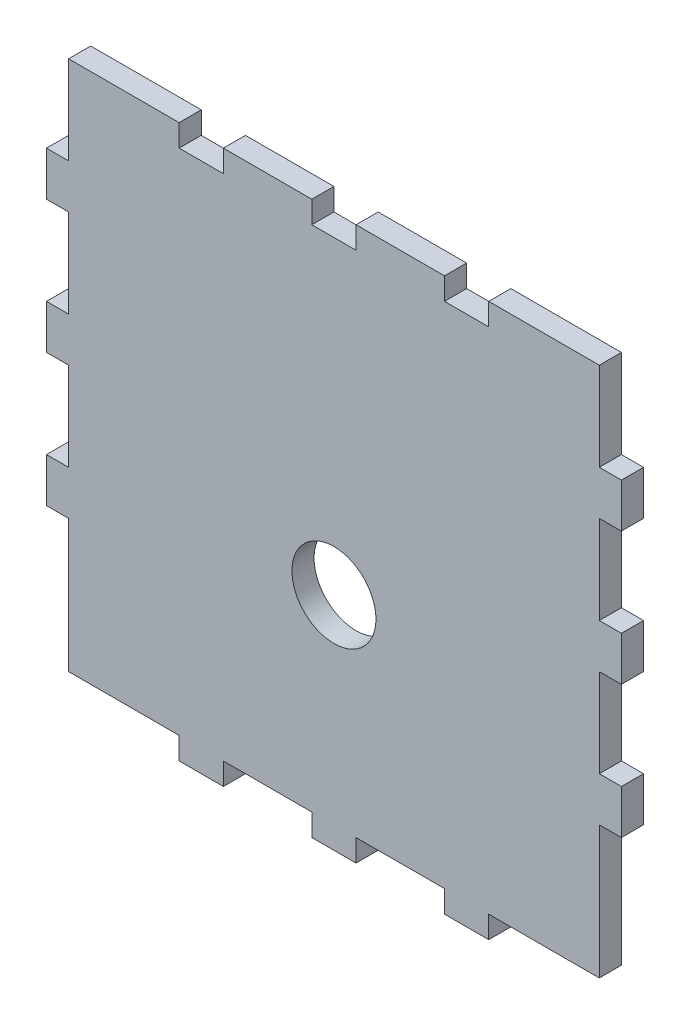
SolidWorks part; units mm, degrees
ref_plane "Ön Düzlem" through (0, 0, 0) normal (0, 0, 1) x (1, 0, 0)
ref_plane "Üst Düzlem" through (0, 0, 0) normal (0, 1, 0) x (1, 0, 0)
ref_plane "Sağ Düzlem" through (0, 0, 0) normal (1, 0, 0) x (0, 0, -1)
sketch "Sketch1" plane through (0, 0, 0) normal (0, 0, 1) x (1, 0, 0)
  line L0 (-35, 60) -> (-35, 55)
  line L1 (-60, -60) -> (-35, -60)
  line L2 (-60, -60) -> (-60, -30)
  line L3 (-60, 60) -> (-35, 60)
  line L4 (60, -60) -> (60, -30)
  line L5 (-60, -60) -> (60, 60) construction
  line L6 (-60, 60) -> (60, -60) construction
  line L7 (-35, 55) -> (-25, 55)
  line L8 (-25, 55) -> (-25, 60)
  line L9 (-35, -60) -> (-35, -65)
  line L10 (-35, -65) -> (-25, -65)
  line L11 (-25, -65) -> (-25, -60)
  line L12 (-5, -60) -> (-5, -65)
  line L13 (-5, -65) -> (5, -65)
  line L14 (5, -65) -> (5, -60)
  line L15 (-5, 55) -> (5, 55)
  line L16 (-5, 60) -> (-5, 55)
  line L17 (5, 55) -> (5, 60)
  line L18 (25, -60) -> (25, -65)
  line L19 (25, -65) -> (35, -65)
  line L20 (35, -65) -> (35, -60)
  line L21 (25, 55) -> (35, 55)
  line L22 (25, 60) -> (25, 55)
  line L23 (35, 55) -> (35, 60)
  line L24 (-60, 40) -> (-65, 40)
  line L25 (-65, 40) -> (-65, 30)
  line L26 (-65, 30) -> (-60, 30)
  line L27 (60, 40) -> (65, 40)
  line L28 (65, 40) -> (65, 30)
  line L29 (65, 30) -> (60, 30)
  line L30 (-65, 10) -> (-65, 0)
  line L31 (-60, 10) -> (-65, 10)
  line L32 (-65, 0) -> (-60, 0)
  line L33 (65, 0) -> (60, 0)
  line L34 (65, 10) -> (65, 0)
  line L35 (60, 10) -> (65, 10)
  line L36 (-65, -20) -> (-65, -30)
  line L37 (-60, -20) -> (-65, -20)
  line L38 (-65, -30) -> (-60, -30)
  line L39 (65, -30) -> (60, -30)
  line L40 (65, -20) -> (65, -30)
  line L41 (60, -20) -> (65, -20)
  line L42 (-25, 60) -> (-5, 60)
  line L43 (5, 60) -> (25, 60)
  line L44 (35, 60) -> (60, 60)
  line L45 (35, -60) -> (60, -60)
  line L46 (5, -60) -> (25, -60)
  line L47 (-25, -60) -> (-5, -60)
  line L48 (-60, -20) -> (-60, 0)
  line L49 (-60, 10) -> (-60, 30)
  line L50 (60, -20) -> (60, 0)
  line L51 (60, 10) -> (60, 30)
  line L52 (60, 40) -> (60, 60)
  line L53 (-60, 40) -> (-60, 60)
  line L54 (-65, -80) -> (-65, -90) [skipped]
  line L55 (-60, -80) -> (-65, -80) [skipped]
  line L56 (-65, -90) -> (-60, -90) [skipped]
  line L57 (65, -90) -> (60, -90) [skipped]
  line L58 (65, -80) -> (65, -90) [skipped]
  line L59 (60, -80) -> (65, -80) [skipped]
  line L60 (65, -60) -> (60, -60) [skipped]
  line L61 (65, -50) -> (65, -60) [skipped]
  line L62 (60, -50) -> (65, -50) [skipped]
  line L63 (-60, -50) -> (-65, -50) [skipped]
  line L64 (-65, -50) -> (-65, -60) [skipped]
  line L65 (-65, -60) -> (-60, -60) [skipped]
  circle A0 centre (0, -15) radius 9.5
  point P0 (0, 0)
  dimension "D13" = 19
  dimension "D1" = 120
  dimension "D2" = 25
  dimension "D3" = 5
  dimension "D4" = 10
  dimension "D6" = 20
  dimension "D7" = 5
  dimension "D8" = 10
  dimension "D9" = 20
  dimension "D11" = 20
  dimension "D12" = 120
  dimension "D14" = 75
  dimension "D15" = 5
  dimension "D5" = 3
  dimension "D10" = 5
extrude "Boss-Extrude1" add sketch "Sketch1" along normal blind 5 contours L27 L52 L44 L23 L21 L22 L43 L17 L15 L16 L42 L8 L7 L0 L3 L49 L31 L30 L32 L48 L37 L36 L38 L2 L1 L9 L10 L11 L47 L12 L13 L14 L46 L18 L19 L20 L45 L4 L39 L40 L41 L50 L33 L34 L35 L51 L29 L28 region at (0, -0.8495, 0)
